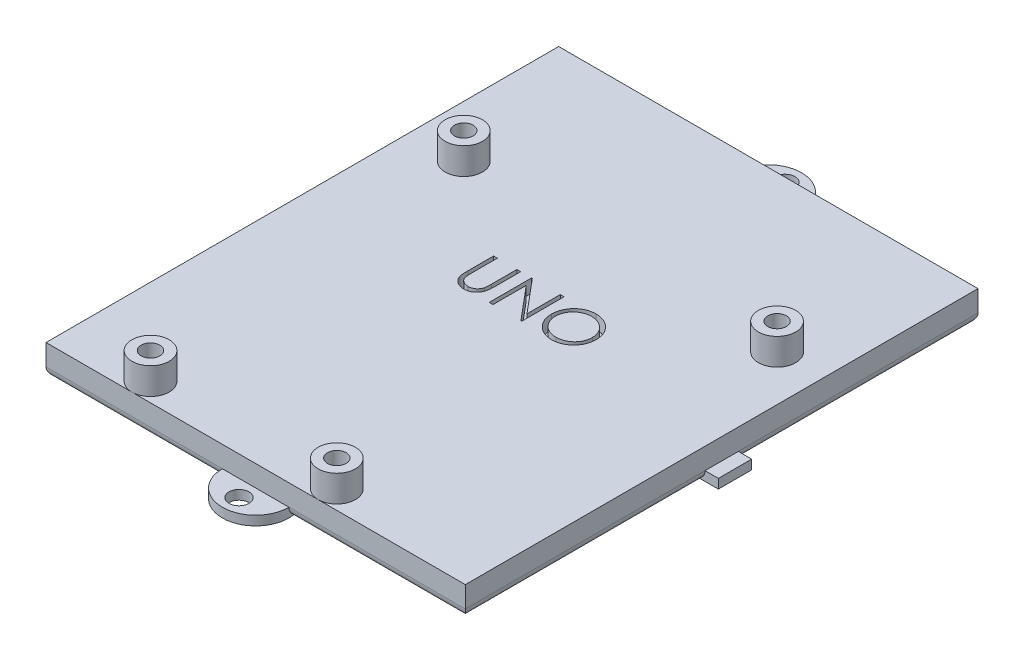
SolidWorks part; units mm, degrees
ref_plane "Front Plane" through (0, 0, 0) normal (0, 0, 1) x (1, 0, 0)
ref_plane "Top Plane" through (0, 0, 0) normal (0, 1, 0) x (1, 0, 0)
ref_plane "Right Plane" through (0, 0, 0) normal (1, 0, 0) x (0, 0, -1)
sketch "Sketch1" plane through (0, 0, 0) normal (0, 1, 0) x (1, 0, 0)
  line L0 (-31.45, 38.45) -> (31.45, 38.45)
  line L5 (-31.45, 38.45) -> (-31.45, -38.45)
  line L6 (-31.45, -38.45) -> (31.45, -38.45)
  line L7 (31.45, 38.45) -> (31.45, -38.45)
  point P11 (-31.45, 0)
  point P12 (0, -38.45)
  dimension "D3" = 76.9
  dimension "D4" = 62.9
extrude "Boss-Extrude1" add sketch "Sketch1" along normal blind 4.575
sketch "Sketch2" plane through (0, 4.575, 0) normal (0, 1, 0) x (1, 0, 0)
  line L0 (9.37, -35.65) -> (9.37, 15.15) construction
  line L1 (24.61, 15.15) -> (9.37, 15.15) construction
  line L2 (9.37, -35.65) -> (-18.57, -35.65) construction
  line L3 (-18.57, -35.65) -> (-18.57, 16.42) construction
  line L4 (0, -38.45) -> (0, 38.45) construction
  line L5 (-31.45, 0) -> (31.45, 0) construction
  line L6 (-18.57, 16.42) -> (-23.65, 16.42) construction
  line L11 (-31.45, 38.45) -> (-31.45, -38.45) construction
  line L12 (-31.45, -38.45) -> (31.45, -38.45) construction
  line L13 (31.45, 38.45) -> (-31.45, 38.45) construction
  line L14 (31.45, -38.45) -> (31.45, 38.45) construction
  circle A0 centre (9.37, -35.65) radius 2.8
  circle A1 centre (24.61, 15.15) radius 2.8
  circle A2 centre (-23.65, 16.42) radius 2.8
  circle A3 centre (-18.57, -35.65) radius 2.8
  circle A4 centre (24.61, 15.15) radius 1.4
  circle A5 centre (9.37, -35.65) radius 1.4
  circle A6 centre (-18.57, -35.65) radius 1.4
  circle A7 centre (-23.65, 16.42) radius 1.4
  point P18 (-15.5663, -26.6274)
  point P19 (-17.1849, -28.017)
  dimension "D7" = 2.8
  dimension "D10" = 1.4
  dimension "D6" = 7.8
  dimension "D1" = 27.94
  dimension "D2" = 15.24
  dimension "D3" = 5.08
  dimension "D4" = 1.27
  dimension "D5" = 50.8
extrude "Boss-Extrude2" add sketch "Sketch2" along normal blind 4
sketch "Sketch3" plane through (0, 4.575, 0) normal (0, 1, 0) x (1, 0, 0)
  circle A0 centre (9.37, -35.65) radius 1.4
  circle A1 centre (-18.57, -35.65) radius 1.4
  circle A2 centre (-23.65, 16.42) radius 1.4
  circle A3 centre (24.61, 15.15) radius 1.4
  circle A4 centre (24.61, 15.15) radius 1.4 construction
  circle A5 centre (-23.65, 16.42) radius 1.4 construction
extrude "Cut-Extrude1" cut sketch "Sketch3" against normal offset from surface (3.575 mm away) 1 up to face at (0, 0, 0)
sketch "Sketch4" plane through (0, 0, 0) normal (0, 1, 0) x (1, 0, 0)
  line L0 (-5, -38.45) -> (5, -38.45)
  line L3 (-31.45, -38.45) -> (31.45, -38.45) construction
  line L4 (0, -38.45) -> (0, -43.45) construction
  arc A0 (-5, -38.45) -> (5, -38.45) centre (0, -38.45) ccw
  circle A2 centre (0, -40.95) radius 1.5
  point P1 (0, 0)
  point P6 (0, -38.45)
  dimension "D2" = 3
  dimension "D3" = 5
extrude "Boss-Extrude3" add sketch "Sketch4" along normal blind 1.4
mirror "Mirror1" about plane through (0, 0, 0) normal (0, 0, 1) of "Boss-Extrude3"
sketch "Sketch5" plane through (0, 4.575, 0) normal (0, 1, 0) x (1, 0, 0)
  line L0 (-15, 0) -> (15, 0) construction
  text T0 "UNO" font "Century Gothic" height in points 24
  point P6 (0, 0)
  dimension "D1" = 30
extrude "Cut-Extrude2" cut sketch "Sketch5" against normal blind 2
sketch "Sketch6" plane through (-31.45, 0, 0) normal (-1, 0, 0) x (0, 0, 1)
  line L0 (-38.45, 0) -> (38.45, 0) construction
  line L1 (-2.5, 0) -> (2.5, 0)
  line L2 (-2.5, 0) -> (-2.5, 1.4)
  line L3 (-2.5, 1.4) -> (2.5, 1.4)
  line L4 (2.5, 0) -> (2.5, 1.4)
  line L5 (43.45, 1.4) -> (38.45, 1.4) construction
  point P6 (0, 0)
  point P7 (0, 1.4)
  dimension "D1" = 5
extrude "Boss-Extrude4" add sketch "Sketch6" along normal blind 2
mirror "Mirror2" about plane through (0, 0, 0) normal (1, 0, 0) of "Boss-Extrude4"
fillet "Fillet1" radius 1.4 8 edges at (-18.225, 0, 38.45) (18.225, 0, 38.45) (31.45, 0, -20.475) (31.45, 0, 20.475) (18.225, 0, -38.45) (-18.225, 0, -38.45) (-31.45, 0, 20.475) (-31.45, 0, -20.475)
